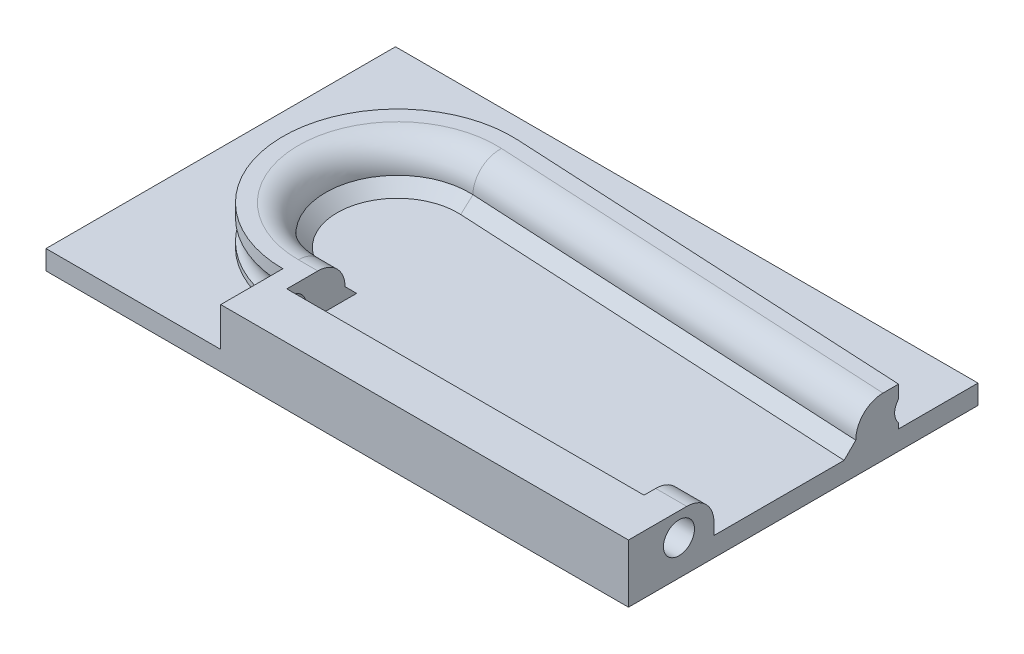
SolidWorks part; units mm, degrees
ref_plane "Front Plane" through (0, 0, 0) normal (0, 0, 1) x (1, 0, 0)
ref_plane "Top Plane" through (0, 0, 0) normal (0, 1, 0) x (1, 0, 0)
ref_plane "Right Plane" through (0, 0, 0) normal (1, 0, 0) x (0, 0, -1)
sketch "Sketch1" plane through (0, 0, 0) normal (0, 1, 0) x (1, 0, 0)
  line L1 (-75, 45) -> (75, 45)
  line L2 (-75, 45) -> (-75, -45)
  line L3 (-75, -45) -> (75, -45)
  line L4 (75, 45) -> (75, -45)
  line L5 (-75, 45) -> (75, -45) construction
  line L6 (-75, -45) -> (75, 45) construction
  point P0 (0, 0)
  dimension "D1" = 150
  dimension "D2" = 90
extrude "Boss-Extrude1" add sketch "Sketch1" along normal blind 5
sketch "Sketch2" plane through (0, 5, 0) normal (0, 1, 0) x (1, 0, 0)
  line L0 (-30, -29) -> (-98.0657, -29) construction
  line L1 (75, -45) -> (-30, -45)
  line L2 (75, -45) -> (75, -29)
  line L4 (-30, -45) -> (-30, -29)
  line L5 (-30, -24) -> (-30, 30) construction
  line L6 (75, 24.5377) -> (-28.4561, 29.9596)
  line L7 (75, -45) -> (75, 45) construction
  line L8 (75, 24.5377) -> (75, -29)
  arc A0 (-28.4561, 29.9596) -> (-30, -29) centre (-30, 0.5) ccw
  dimension "D2" = 59
  dimension "D3" = 87
  dimension "D4" = 105
  dimension "D1" = 16
  dimension "D5" = 16
extrude "Boss-Extrude2" add sketch "Sketch2" along normal blind 10
sketch "Sketch3" plane through (75, 0, 0) normal (1, 0, 0) x (0, 0, -1)
  line L0 (24.5377, 5) -> (-48.4082, 5) construction
  line L1 (-45, 15) -> (-45, 0) construction
  circle A0 centre (-32, 9) radius 4
  dimension "D1" = 8
  dimension "D2" = 4
  dimension "D3" = 13
ref_plane "Plane1" through (0, 9, 0) normal (0, 1, 0) x (1, 0, 0)
sketch "Sketch4" plane through (0, 9, 0) normal (0, 1, 0) x (1, 0, 0)
  line L0 (75, -32) -> (-30, -32)
  line L1 (75, -36) -> (75, -28) construction
  line L2 (75, 27.5418) -> (-28.2991, 32.9555)
  line L3 (75, 24.5377) -> (-28.4561, 29.9596) construction
  line L4 (75, 24.5377) -> (75, 45) construction
  line L8 (75, 27.5418) -> (96.6855, 26.4053)
  arc A0 (-30, -32) -> (-28.2991, 32.9555) centre (-30, 0.5) cw
  dimension "D1" = 32.5
  dimension "D2" = 3
  dimension "D3" = 3
  dimension "D4" = 21.7153
sweep "Cut-Sweep1" cut profiles "Sketch3" path "Sketch4"
sketch "Sketch5" plane through (0, 15, 0) normal (0, 1, 0) x (1, 0, 0)
  line L0 (-25, -18) -> (-25, -33)
  line L1 (-25, -33) -> (67, -33)
  line L2 (75, -23) -> (75, 13.5226)
  line L3 (75, 24.5377) -> (-28.4561, 29.9596) construction
  line L6 (67, -33) -> (67, -23)
  line L7 (67, -23) -> (75, -23)
  line L8 (-30, -18) -> (-25, -18)
  line L10 (-29.0318, 18.9746) -> (75, 13.5226)
  line L12 (64, -34) -> (64, 14.0991)
  line L13 (64, 14.0991) -> (-29.0318, 18.9746)
  line L14 (-19, -14.3745) -> (-19, -34)
  line L15 (-19, -34) -> (64, -34)
  arc A3 (-29.0318, 18.9746) -> (-19, -14.3745) centre (-30, 0.5) ccw
  arc A4 (-29.0318, 18.9746) -> (-30, -18) centre (-30, 0.5) ccw
  point P0 (-25, -18)
  dimension "D4" = 8
  dimension "D2" = 100
  dimension "D3" = 15
  dimension "D5" = 10
  dimension "D1" = 11
extrude "Cut-Extrude1" cut sketch "Sketch5" against normal blind 10
chamfer "Chamfer2" distance 3 angle 45 3 edges at (-27.5, 5, 18) (22.9841, 5, -16.2486) (-48.4937, 5, -0.9843)
fillet "Fillet1" radius 7 4 edges at (-27.5, 15, 18) (-48.4937, 15, -0.9843) (22.9841, 15, -16.2486) (71, 15, 23)
